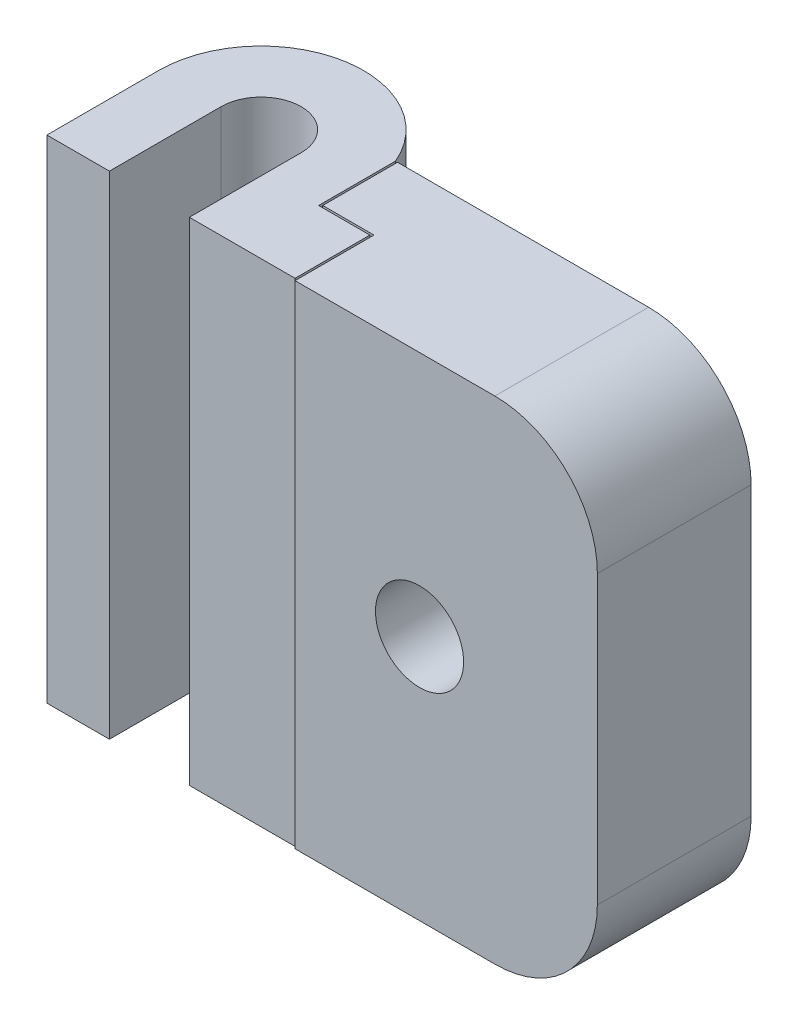
SolidWorks part; units mm, degrees
ref_plane "Front Plane" through (0, 0, 0) normal (0, 0, 1) x (1, 0, 0)
ref_plane "Top Plane" through (0, 0, 0) normal (0, 1, 0) x (1, 0, 0)
ref_plane "Right Plane" through (0, 0, 0) normal (1, 0, 0) x (0, 0, -1)
sketch "Sketch4" plane through (0, 0, 0) normal (0, 1, 0) x (1, 0, 0)
  line L1 (21.95, 0) -> (21.95, 1.95)
  line L2 (21.95, 1.95) -> (4.6041, 1.95)
  line L3 (1.95, 0) -> (1.95, -5.55)
  line L4 (1.95, -5.55) -> (21.95, -5.55)
  line L5 (21.95, -5.55) -> (21.95, 0)
  line L8 (-5, 0) -> (-5, -5.55)
  line L9 (-5, -5.55) -> (-1.95, -5.55)
  line L10 (-1.95, 0) -> (-1.95, -5.55)
  arc A0 (1.95, 0) -> (-1.95, 0) centre (0, 0) ccw
  arc A1 (4.6041, 1.95) -> (-5, 0) centre (0, 0) ccw
  dimension "D1" = 3.9
  dimension "D2" = 10
  dimension "D3" = 5.55
  dimension "D4" = 20
extrude "Boss-Extrude3" add sketch "Sketch4" along normal blind 24
fillet "Fillet1" radius 5 2 edges at (21.95, 0, 1.8) (21.95, 24, 1.8)
sketch "Sketch10" plane through (0, 0, -1.95) normal (0, 0, -1) x (-1, 0, 0)
  line L0 (-21.95, 19) -> (-21.95, 5) construction
  line L2 (-21.95, 12) -> (-4.6041, 12) construction
  line L3 (-4.6041, 24) -> (-4.6041, 0) construction
  circle A0 centre (-13.277, 12) radius 4.1
  point P4 (-21.95, 12)
  point P5 (-13.277, 12)
  dimension "D1" = 8.2
extrude "Cut-Extrude3" cut sketch "Sketch10" against normal blind 3
sketch "Sketch11" plane through (0, 0, 1.05) normal (0, 0, -1) x (-1, 0, 0)
  circle A0 centre (-13.277, 12) radius 2.15
  circle A1 centre (-13.277, 12) radius 4.1
  circle A2 centre (-13.277, 12) radius 4.1 construction
  dimension "D2" = 4.3
  dimension "D1" = 0
extrude "Cut-Extrude4" cut sketch "Sketch11" against normal through all
sketch "Sketch13" plane through (0, 0, 0) normal (0, -1, 0) x (1, 0, 0)
  line L10 (4.6041, -1.95) -> (4.6041, 1.8)
  line L11 (4.6041, 1.8) -> (7.1041, 1.8)
  line L12 (7.1041, 1.8) -> (7.1041, 5.55)
  line L13 (1.95, 5.55) -> (16.95, 5.55) construction
  line L14 (4.7041, -1.95) -> (4.7041, 1.7)
  line L15 (4.7041, 1.7) -> (7.2041, 1.7)
  line L16 (7.2041, 1.7) -> (7.2041, 5.55)
  line L17 (4.6041, -1.95) -> (4.7041, -1.95)
  line L18 (7.1041, 5.55) -> (7.2041, 5.55)
  dimension "D1" = 2.5
  dimension "D2" = 0.1
extrude "Cut-Extrude5" cut sketch "Sketch13" against normal through all
sketch "Sketch14" plane through (0, 0, 5.55) normal (0, 0, 1) x (1, 0, 0)
  line L4 (1.95, 0) -> (7.1041, 0)
  line L5 (7.1041, 0) -> (7.1041, 24)
  line L6 (7.1041, 24) -> (1.95, 24)
  line L7 (1.95, 24) -> (1.95, 0)
  line L8 (1.95, 0) -> (7.1041, 0)
  line L9 (7.1041, 0) -> (7.1041, 24)
  line L10 (7.1041, 24) -> (1.95, 24)
  line L11 (1.95, 24) -> (1.95, 0)
  line L12 (-5, 0) -> (-1.95, 0)
  line L13 (-1.95, 0) -> (-1.95, 24)
  line L14 (-1.95, 24) -> (-5, 24)
  line L15 (-5, 24) -> (-5, 0)
  line L16 (-5, 0) -> (-1.95, 0)
  line L17 (-1.95, 0) -> (-1.95, 24)
  line L18 (-1.95, 24) -> (-5, 24)
  line L19 (-5, 24) -> (-5, 0)
  dimension "D1" = 0
  dimension "D2" = 0
extrude "Cut-Extrude6" cut sketch "Sketch14" against normal blind 0.1
